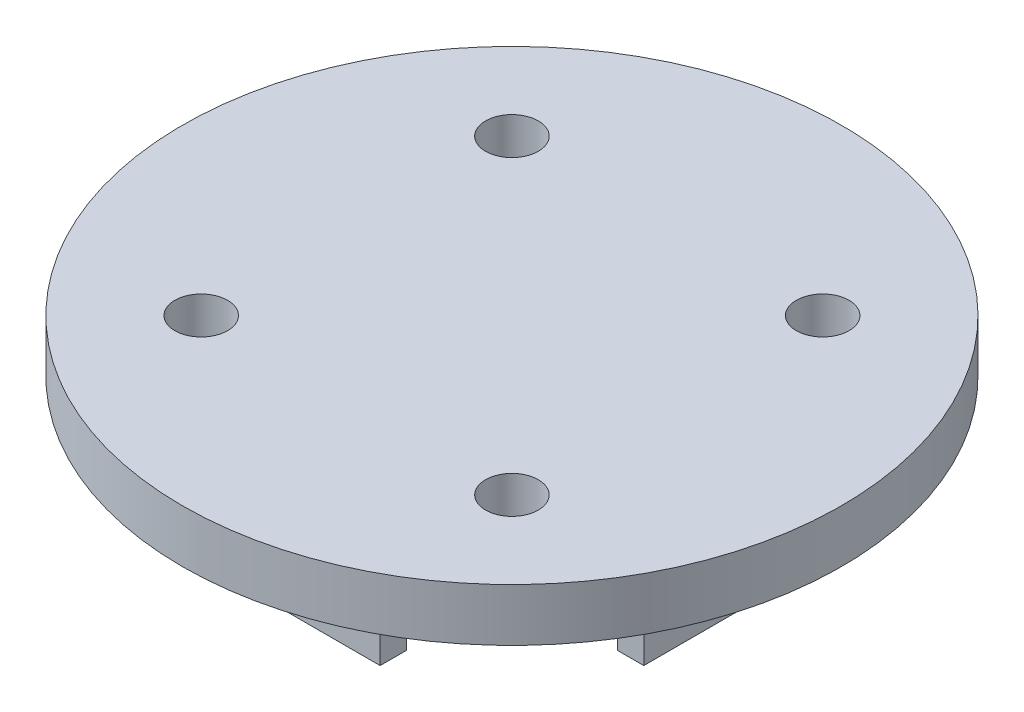
SolidWorks part; units mm, degrees
ref_plane "前视基准面" through (0, 0, 0) normal (0, 0, 1) x (1, 0, 0)
ref_plane "上视基准面" through (0, 0, 0) normal (0, 1, 0) x (1, 0, 0)
ref_plane "右视基准面" through (0, 0, 0) normal (1, 0, 0) x (0, 0, -1)
sketch "草图1" plane through (0, 0, 0) normal (0, 1, 0) x (1, 0, 0)
  circle A0 centre (0, 0) radius 37.5
extrude "凸台-拉伸1" add sketch "草图1" along normal blind 6 contours A0
sketch "草图3" plane through (0, 6, 0) normal (0, 1, 0) x (1, 0, 0)
sketch "草图4" plane through (0, 0, 0) normal (0, 1, 0) x (1, 0, 0)
  line L0 (0, 25) -> (0, 0)
  line L1 (0, 0) -> (-17.6777, 17.6777)
  circle A0 centre (0, 0) radius 25
  circle A1 centre (-17.6777, 17.6777) radius 3
  dimension "D1" = 45
extrude "切除-拉伸2" cut sketch "草图4" along normal through all contours A1
pattern_circular "阵列(圆周)1" count 4 every 90 of "切除-拉伸2"
ref_plane "基准面1" through (0, 0, 0) normal (0, -1, 0) x (-1, 0, 0)
sketch "草图5" plane through (0, 0, 0) normal (0, -1, 0) x (-1, 0, 0)
  line L2 (-9, 24) -> (9, 24)
  line L3 (-9, 24) -> (-9, 21)
  line L4 (-9, 21) -> (9, 21)
  line L5 (9, 24) -> (9, 21)
  line L6 (-9, 24) -> (9, 21) construction
  line L7 (-9, 21) -> (9, 24) construction
  line L9 (21, 9) -> (24, 9)
  line L10 (21, 9) -> (21, -9)
  line L11 (21, -9) -> (24, -9)
  line L12 (24, 9) -> (24, -9)
  line L13 (21, 9) -> (24, -9) construction
  line L14 (21, -9) -> (24, 9) construction
  dimension "D1" = 9
  dimension "D2" = 9
  dimension "D3" = 9
  dimension "D4" = 9
  dimension "D5" = 21
  dimension "D6" = 21
  dimension "D7" = 3
  dimension "D8" = 3
extrude "凸台-拉伸2" add sketch "草图5" along normal blind 12 contours L4 L5 L2 L3
extrude "凸台-拉伸3" add sketch "草图5<3>" along normal blind 12
sketch "草图5<3>" plane through (0, 0, 0) normal (0, -1, 0) x (-1, 0, 0) same geometry as "草图5"
mirror "镜向3" about plane through (0, 0, 0) normal (0, 0, 1) of "凸台-拉伸2"
mirror "镜向4" about plane through (0, 0, 0) normal (1, 0, 0) of "凸台-拉伸3"
ref_plane "基准面2" through (0, 0, 24) normal (0, 0, 1) x (1, 0, 0)
sketch "草图6" plane through (0, 0, 24) normal (0, 0, 1) x (1, 0, 0)
  line L0 (-9, 0) -> (9, -12)
  circle A0 centre (0, -6) radius 2.1
extrude "切除-拉伸3" cut sketch "草图6" against normal through all contours A0
ref_plane "基准面4" through (24, 0, 0) normal (1, 0, 0) x (0, 0, -1)
sketch "草图7" plane through (24, 0, 0) normal (1, 0, 0) x (0, 0, -1)
  line L0 (-9, 0) -> (9, -12)
  circle A0 centre (0, -6) radius 2.1
extrude "切除-拉伸4" cut sketch "草图7" against normal through all contours A0
